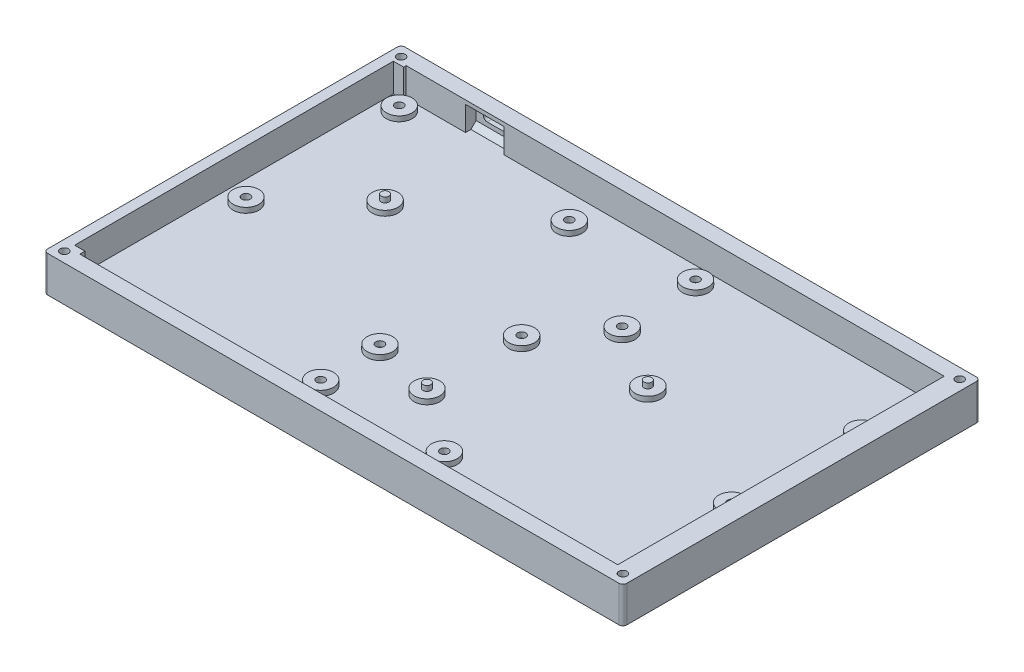
SolidWorks part; units mm, degrees
ref_plane "Front Plane" through (0, 0, 0) normal (0, 0, 1) x (1, 0, 0)
ref_plane "Top Plane" through (0, 0, 0) normal (0, 1, 0) x (1, 0, 0)
ref_plane "Right Plane" through (0, 0, 0) normal (1, 0, 0) x (0, 0, -1)
sketch "Sketch1" plane through (0, 0, 0) normal (0, 1, 0) x (1, 0, 0)
  line L1 (44.992, 213.0031) -> (269.802, 213.0031)
  line L2 (44.992, 213.0031) -> (44.992, 351.7031)
  line L3 (44.992, 351.7031) -> (269.802, 351.7031)
  line L4 (269.802, 213.0031) -> (269.802, 351.7031)
  dimension "D1" = 138.7
  dimension "D2" = 224.81
extrude "bottom_plate" add sketch "Sketch1" along normal blind 3
sketch "Sketch2" plane through (0, 3, 0) normal (0, 1, 0) x (1, 0, 0)
  line L9 (44.992, 213.0031) -> (52.992, 213.0031)
  line L10 (44.992, 213.0031) -> (44.992, 221.0031)
  line L11 (44.992, 221.0031) -> (52.992, 221.0031)
  line L12 (52.992, 213.0031) -> (52.992, 221.0031)
  line L13 (269.802, 213.0031) -> (262.802, 213.0031)
  line L14 (269.802, 213.0031) -> (269.802, 220.0031)
  line L15 (269.802, 220.0031) -> (262.802, 220.0031)
  line L16 (262.802, 213.0031) -> (262.802, 220.0031)
  line L17 (269.802, 351.7031) -> (262.802, 351.7031)
  line L18 (269.802, 351.7031) -> (269.802, 344.7031)
  line L19 (269.802, 344.7031) -> (262.802, 344.7031)
  line L20 (262.802, 351.7031) -> (262.802, 344.7031)
  line L21 (44.992, 351.7031) -> (52.992, 351.7031)
  line L22 (44.992, 351.7031) -> (44.992, 344.7031)
  line L23 (44.992, 344.7031) -> (52.992, 344.7031)
  line L24 (52.992, 351.7031) -> (52.992, 344.7031)
  dimension "D1" = 8
  dimension "D2" = 7
extrude "side_walls" add sketch "Sketch2" along normal blind 11
sketch "Sketch11" plane through (0, 3, 0) normal (0, 1, 0) x (1, 0, 0)
  line L0 (52.992, 221.0031) -> (44.992, 221.0031) construction
  line L1 (44.992, 344.7031) -> (48.992, 344.7031)
  line L2 (44.992, 344.7031) -> (44.992, 221.0031)
  line L3 (44.992, 221.0031) -> (48.992, 221.0031)
  line L4 (48.992, 344.7031) -> (48.992, 221.0031)
  line L5 (262.802, 220.0031) -> (262.802, 213.0031) construction
  line L6 (52.992, 213.0031) -> (262.802, 213.0031)
  line L7 (52.992, 213.0031) -> (52.992, 219.0031)
  line L8 (52.992, 219.0031) -> (261.802, 219.0031)
  line L9 (262.802, 213.0031) -> (262.802, 219.0031)
  line L11 (269.802, 219.0031) -> (262.802, 219.0031)
  line L12 (269.802, 219.0031) -> (269.802, 345.7031)
  line L13 (269.802, 345.7031) -> (262.802, 345.7031)
  line L14 (261.802, 219.0031) -> (261.802, 345.7031)
  line L15 (52.992, 344.7031) -> (52.992, 351.7031) construction
  line L16 (262.802, 351.7031) -> (52.992, 351.7031)
  line L17 (262.802, 351.7031) -> (262.802, 345.7031)
  line L18 (261.802, 345.7031) -> (90.992, 345.7031)
  line L19 (52.992, 351.7031) -> (52.992, 345.7031)
  line L20 (75.992, 345.7031) -> (52.992, 345.7031)
  line L22 (90.992, 345.7031) -> (90.992, 349.8031)
  line L23 (90.992, 349.8031) -> (75.992, 349.8031)
  line L24 (75.992, 345.7031) -> (75.992, 349.8031)
  line L25 (269.802, 220.0031) -> (269.802, 344.7031) construction
  dimension "D1" = 8
  dimension "D2" = 6
  dimension "D3" = 6
  dimension "D4" = 4
  dimension "D5" = 4.1
  dimension "D6" = 31
  dimension "D7" = 15
extrude "usb_cutout" add sketch "Sketch11" along normal up to surface (11 mm away) up to face at (266.302, 14, -216.5031)
hole_wizard "CSK for M3 SFHCS1" positions "Sketch5" profile "Sketch6" countersink size "M3" standard "ANSI Metric" end condition through all
sketch "Sketch5" plane through (0, 0, 0) normal (0, -1, 0) x (-1, 0, 0)
  point P42 (-48.992, 217.0037)
  point P45 (-265.7999, 217.0037)
  point P48 (-265.7999, 347.7031)
  point P51 (-48.992, 347.7031)
sketch "Sketch6" plane through (48.992, 0, -217.0037) normal (1, 0, 0) x (0, 0, -1)
  line L0 (0, 0) -> (0, 14)
  line L1 (0, 14) -> (1.6, 14)
  line L2 (1.6, 14) -> (1.6, 1.76)
  line L3 (1.6, 1.76) -> (3.36, 0)
  line L5 (3.36, 0) -> (0, 0)
  line L6 (-1.6, 1.76) -> (-3.36, 0) construction
  line L11 (0, -6.35) -> (0, 107.95) construction
  dimension "Thru Hole Dia." = 3.2
  dimension "Thru Hole Depth" = 14
  dimension "Near C'Sink Dia." = 6.72
  dimension "Near C'Sink Angle" = 90
fillet "Fillet1" radius 1.5 4 edges at (44.992, 7, -351.7031) (44.992, 7, -213.0031) (269.802, 7, -351.7031) (269.802, 7, -213.0031)
sketch "Sketch14" plane through (0, 0, -349.8031) normal (0, 0, 1) x (1, 0, 0)
  line L0 (44.992, 14) -> (44.992, 0) construction
  line L9 (80.3002, 6.7) -> (86.4707, 6.7)
  line L10 (78.8002, 8.2) -> (78.8002, 8.5905)
  line L11 (80.3002, 10.0905) -> (86.4707, 10.0905)
  line L12 (87.9707, 8.2) -> (87.9707, 8.5905)
  line L13 (268.302, 0) -> (46.492, 0) construction
  arc A4 (78.8002, 8.5905) -> (80.3002, 10.0905) centre (80.3002, 8.5905) cw
  arc A5 (80.3002, 6.7) -> (78.8002, 8.2) centre (80.3002, 8.2) cw
  arc A6 (86.4707, 6.7) -> (87.9707, 8.2) centre (86.4707, 8.2) ccw
  arc A7 (86.4707, 10.0905) -> (87.9707, 8.5905) centre (86.4707, 8.5905) cw
  dimension "D1" = 9.1705
  dimension "D5" = 1.5
  dimension "D2" = 3.3905
  dimension "D3" = 33.8083
  dimension "D4" = 6.7
extrude "usb-c port" cut sketch "Sketch14" against normal blind 10
sketch "Sketch18" plane through (0, 14, 0) normal (0, 1, 0) x (1, 0, 0)
  line L1 (75.992, 345.7031) -> (90.992, 345.7031)
  line L2 (75.992, 345.7031) -> (75.992, 349.8031)
  line L3 (75.992, 349.8031) -> (90.992, 349.8031)
  line L4 (90.992, 345.7031) -> (90.992, 349.8031)
extrude "Boss-Extrude1" add sketch "Sketch18" against normal blind 1.5
chamfer "Chamfer1" distance 2 angle 45 2 edges at (83.492, 3, -349.8031) (83.492, 12.5, -349.8031)
sketch "Sketch16" plane through (0, 3, 0) normal (0, 1, 0) x (1, 0, 0)
  circle A0 centre (55.992, 340.0037) radius 5
  circle A1 centre (56.992, 279.5037) radius 5
  circle A2 centre (132.492, 256.0037) radius 5
  circle A4 centre (253.992, 271.0037) radius 5
  circle A5 centre (254.992, 320.5037) radius 5
  circle A6 centre (156.992, 286.5037) radius 5
  circle A7 centre (171.992, 339.0037) radius 5
  circle A8 centre (127.492, 334.5037) radius 5
  circle A9 centre (173.492, 309.0037) radius 5
  circle A10 centre (198.492, 294.0037) radius 5
  circle A11 centre (180.992, 232.5037) radius 5
  circle A12 centre (84.992, 305.5037) radius 5
  circle A15 centre (156.492, 250.2537) radius 5
  circle A29 centre (132.992, 232.5037) radius 5
  point P2 (55.992, 340.0037)
  point P5 (127.492, 334.5037)
  point P8 (84.992, 305.5037)
  point P9 (56.992, 279.5037)
  point P10 (132.492, 256.0037)
  point P11 (0, 0)
  point P14 (156.492, 250.2537)
  point P17 (180.992, 232.5037)
  point P20 (132.992, 232.5037)
  point P23 (156.992, 286.5037)
  point P26 (171.992, 339.0037)
  point P29 (173.492, 309.0037)
  point P32 (198.492, 294.0037)
  point P35 (253.992, 271.0037)
  point P38 (254.992, 320.5037)
  dimension "D1" = 10
extrude "pcb_support" add sketch "Sketch16" along normal blind 2 contours A0 | A12 | A1 | A7 | A8 | A6 | A11 | A10 | A5 | A4 | A9 | A2 | A15 | A29 region at (55.992, 3, -340.0037) region at (56.992, 3, -279.5037) region at (253.992, 3, -271.0037) region at (254.992, 3, -320.5037) region at (156.992, 3, -286.5037) region at (171.992, 3, -339.0037) region at (127.492, 3, -334.5037) region at (198.492, 3, -294.0037) region at (180.992, 3, -232.5037) region at (84.992, 3, -305.5037)
sketch "Sketch17" plane through (0, 5, 0) normal (0, 1, 0) x (1, 0, 0)
  circle A0 centre (84.992, 305.5037) radius 1.5
  circle A1 centre (198.492, 294.0037) radius 1.5
  circle A2 centre (84.992, 305.5037) radius 5 construction
  circle A3 centre (156.492, 250.2537) radius 1.5
  dimension "D1" = 3
  dimension "D2" = 3
  dimension "D3" = 3
extrude "alignment_posts" add sketch "Sketch17" along normal blind 2
sketch "Sketch20" plane through (0, 5, 0) normal (0, 1, 0) x (1, 0, 0)
  circle A0 centre (55.992, 340.0037) radius 1.6
  circle A1 centre (127.492, 334.5037) radius 1.6
  circle A2 centre (56.992, 279.5037) radius 1.6
  circle A3 centre (132.492, 256.0037) radius 1.6
  circle A4 centre (132.992, 232.5037) radius 1.6
  circle A5 centre (180.992, 232.5037) radius 1.6
  circle A6 centre (156.992, 286.5037) radius 1.6
  circle A7 centre (253.992, 271.0037) radius 1.6
  circle A8 centre (173.492, 309.0037) radius 1.6
  circle A9 centre (171.992, 339.0037) radius 1.6
  circle A10 centre (254.992, 320.5037) radius 1.6
  dimension "D1" = 3.2
extrude "pcb screw clearance" cut sketch "Sketch20" against normal blind 2.15
sketch "Sketch21" plane through (0, 2.85, 0) normal (0, 1, 0) x (1, 0, 0)
  line L0 (154.242, 283.7537) -> (159.742, 283.7537)
  line L1 (53.242, 342.7537) -> (58.742, 342.7537)
  line L2 (53.242, 342.7537) -> (53.242, 337.2537)
  line L3 (53.242, 337.2537) -> (58.742, 337.2537)
  line L4 (58.742, 342.7537) -> (58.742, 337.2537)
  line L5 (53.242, 342.7537) -> (58.742, 337.2537) construction
  line L6 (53.242, 337.2537) -> (58.742, 342.7537) construction
  line L7 (124.742, 337.2537) -> (130.242, 337.2537)
  line L8 (124.742, 337.2537) -> (124.742, 331.7537)
  line L9 (124.742, 331.7537) -> (130.242, 331.7537)
  line L10 (130.242, 337.2537) -> (130.242, 331.7537)
  line L11 (124.742, 337.2537) -> (130.242, 331.7537) construction
  line L12 (124.742, 331.7537) -> (130.242, 337.2537) construction
  line L13 (54.242, 282.2537) -> (59.742, 282.2537)
  line L14 (54.242, 282.2537) -> (54.242, 276.7537)
  line L15 (54.242, 276.7537) -> (59.742, 276.7537)
  line L16 (59.742, 282.2537) -> (59.742, 276.7537)
  line L17 (54.242, 282.2537) -> (59.742, 276.7537) construction
  line L18 (54.242, 276.7537) -> (59.742, 282.2537) construction
  line L19 (129.742, 258.7537) -> (135.242, 258.7537)
  line L20 (129.742, 258.7537) -> (129.742, 253.2537)
  line L21 (129.742, 253.2537) -> (135.242, 253.2537)
  line L22 (135.242, 258.7537) -> (135.242, 253.2537)
  line L23 (129.742, 258.7537) -> (135.242, 253.2537) construction
  line L24 (129.742, 253.2537) -> (135.242, 258.7537) construction
  line L25 (135.742, 235.2537) -> (130.242, 235.2537)
  line L26 (135.742, 235.2537) -> (135.742, 229.7537)
  line L27 (135.742, 229.7537) -> (130.242, 229.7537)
  line L28 (130.242, 235.2537) -> (130.242, 229.7537)
  line L29 (135.742, 235.2537) -> (130.242, 229.7537) construction
  line L30 (135.742, 229.7537) -> (130.242, 235.2537) construction
  line L31 (178.242, 229.7537) -> (183.742, 229.7537)
  line L32 (178.242, 229.7537) -> (178.242, 235.2537)
  line L33 (178.242, 235.2537) -> (183.742, 235.2537)
  line L34 (183.742, 229.7537) -> (183.742, 235.2537)
  line L35 (178.242, 229.7537) -> (183.742, 235.2537) construction
  line L36 (178.242, 235.2537) -> (183.742, 229.7537) construction
  line L37 (256.742, 273.7537) -> (251.242, 273.7537)
  line L38 (256.742, 273.7537) -> (256.742, 268.2537)
  line L39 (256.742, 268.2537) -> (251.242, 268.2537)
  line L40 (251.242, 273.7537) -> (251.242, 268.2537)
  line L41 (256.742, 273.7537) -> (251.242, 268.2537) construction
  line L42 (256.742, 268.2537) -> (251.242, 273.7537) construction
  line L43 (170.742, 306.2537) -> (176.242, 306.2537)
  line L44 (170.742, 306.2537) -> (170.742, 311.7537)
  line L45 (170.742, 311.7537) -> (176.242, 311.7537)
  line L46 (176.242, 306.2537) -> (176.242, 311.7537)
  line L47 (170.742, 306.2537) -> (176.242, 311.7537) construction
  line L48 (170.742, 311.7537) -> (176.242, 306.2537) construction
  line L49 (169.242, 336.2537) -> (174.742, 336.2537)
  line L50 (169.242, 336.2537) -> (169.242, 341.7537)
  line L51 (169.242, 341.7537) -> (174.742, 341.7537)
  line L52 (174.742, 336.2537) -> (174.742, 341.7537)
  line L53 (169.242, 336.2537) -> (174.742, 341.7537) construction
  line L54 (169.242, 341.7537) -> (174.742, 336.2537) construction
  line L55 (252.242, 317.7537) -> (257.742, 317.7537)
  line L56 (252.242, 317.7537) -> (252.242, 323.2537)
  line L57 (252.242, 323.2537) -> (257.742, 323.2537)
  line L58 (257.742, 317.7537) -> (257.742, 323.2537)
  line L59 (252.242, 317.7537) -> (257.742, 323.2537) construction
  line L60 (252.242, 323.2537) -> (257.742, 317.7537) construction
  line L61 (154.242, 283.7537) -> (154.242, 289.2537)
  line L62 (154.242, 289.2537) -> (159.742, 289.2537)
  line L63 (159.742, 283.7537) -> (159.742, 289.2537)
  line L64 (154.242, 283.7537) -> (159.742, 289.2537) construction
  line L65 (154.242, 289.2537) -> (159.742, 283.7537) construction
  point P0 (55.992, 340.0037)
  point P6 (127.492, 334.5037)
  point P12 (56.992, 279.5037)
  point P18 (132.492, 256.0037)
  point P24 (132.992, 232.5037)
  point P30 (180.992, 232.5037)
  point P36 (253.992, 271.0037)
  point P42 (173.492, 309.0037)
  point P48 (171.992, 339.0037)
  point P54 (254.992, 320.5037)
  point P60 (156.992, 286.5037)
  dimension "D1" = 5.5
extrude "captive nut hole" cut sketch "Sketch21" against normal blind 1.8
